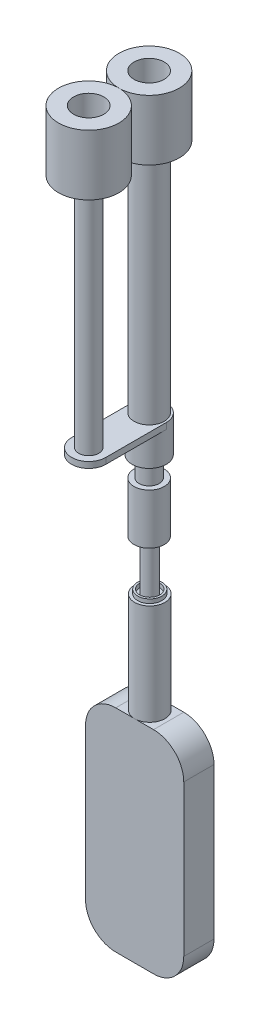
SolidWorks part; units mm, degrees
ref_plane "Front Plane" through (0, 0, 0) normal (0, 0, 1) x (1, 0, 0)
ref_plane "Top Plane" through (0, 0, 0) normal (0, 1, 0) x (1, 0, 0)
ref_plane "Right Plane" through (0, 0, 0) normal (1, 0, 0) x (0, 0, -1)
sketch "Sketch1" plane through (0, 0, 0) normal (0, 0, 1) x (1, 0, 0)
  line L1 (16.25, 35) -> (-16.25, 35)
  line L2 (16.25, 35) -> (16.25, -35)
  line L3 (16.25, -35) -> (-16.25, -35)
  line L4 (-16.25, 35) -> (-16.25, -35)
  line L5 (16.25, 35) -> (-16.25, -35) construction
  line L6 (16.25, -35) -> (-16.25, 35) construction
  point P0 (0, 0)
  dimension "D1" = 32.5
  dimension "D2" = 70
extrude "Boss-Extrude1" add sketch "Sketch1" along normal blind 10
fillet "Fillet1" radius 10 4 edges at (-16.25, -35, 5) (16.25, -35, 5) (16.25, 35, 5) (-16.25, 35, 5)
scale "Scale1" scale about centroid uniform scaling yes scale factor 1.5
sketch "Sketch2" plane through (0, 52.5, 0) normal (0, 1, 0) x (1, 0, 0)
  circle A0 centre (0, -5) radius 7.5
extrude "Boss-Extrude2" add sketch "Sketch2" along normal blind 50
sketch "Sketch3" plane through (0, 102.5, 0) normal (0, 1, 0) x (1, 0, 0)
  circle A0 centre (0, -5) radius 3.5
  dimension "D1" = 7
extrude "Boss-Extrude3" add sketch "Sketch3" along normal blind 25
sketch "Sketch4" plane through (0, 127.5, 0) normal (0, 1, 0) x (1, 0, 0)
  circle A0 centre (0, -5.3071) radius 7.5
  dimension "D1" = 15
extrude "Boss-Extrude4" add sketch "Sketch4" along normal blind 25 contours A0
sketch "Sketch5" plane through (0, 152.5, 0) normal (0, 1, 0) x (1, 0, 0)
  circle A0 centre (0, -5.3071) radius 5
extrude "Boss-Extrude5" add sketch "Sketch5" along normal blind 10
sketch "Sketch6" plane through (0, 162.5, 0) normal (0, 1, 0) x (1, 0, 0)
  circle A0 centre (0, -5.3071) radius 8.5
  dimension "D1" = 17
extrude "Boss-Extrude6" add sketch "Sketch6" along normal blind 15
sketch "Sketch7" plane through (0, 177.5, 0) normal (0, 1, 0) x (1, 0, 0)
  circle A0 centre (0, -5.3071) radius 7.5
  dimension "D1" = 15
extrude "Boss-Extrude7" add sketch "Sketch7" along normal blind 120
ref_plane "Plane3" through (0, 102.5, 0) normal (0, 1, 0) x (1, 0, 0)
sketch "Sketch9" plane through (0, 102.5, 0) normal (0, 1, 0) x (1, 0, 0)
  circle A0 centre (0, -5) radius 6
  circle A1 centre (0, -5) radius 5
  dimension "D1" = 12
  dimension "D2" = 10
extrude "Boss-Extrude8" add sketch "Sketch9" along normal blind 2
ref_plane "Plane4" through (0, 177.5, 0) normal (0, 1, 0) x (1, 0, 0)
sketch "Sketch10" plane through (0, 177.5, 0) normal (0, 1, 0) x (1, 0, 0)
  line L0 (-8.5, -5.3071) -> (-8.5, -35.3071)
  line L1 (8.5, -5.3071) -> (8.5, -35.3071)
  arc A0 (8.5, -5.3071) -> (-8.5, -5.3071) centre (0, -5.3071) ccw
  arc A1 (-8.5, -35.3071) -> (8.5, -35.3071) centre (0, -35.3071) ccw
  dimension "D1" = 30
  dimension "D2" = 30
extrude "Boss-Extrude9" add sketch "Sketch10" along normal blind 3
ref_plane "Plane5" through (0, 297.5, 0) normal (0, 1, 0) x (1, 0, 0)
sketch "Sketch11" plane through (0, 180.5, 0) normal (0, 1, 0) x (1, 0, 0)
  circle A0 centre (0, -35.3071) radius 5
  arc A1 (-8.5, -35.3071) -> (8.5, -35.3071) centre (0, -35.3071) ccw construction
  dimension "D2" = 10
  dimension "D1" = 0
extrude "Boss-Extrude10" add sketch "Sketch11" along normal up to surface (117 mm away) up to plane "Plane5"
sketch "Sketch12" plane through (0, 297.5, 0) normal (0, 1, 0) x (1, 0, 0)
  circle A0 centre (0, -5.3071) radius 15
  circle A1 centre (0, -35.3071) radius 15
  circle M3 centre (0, -5.3071) radius 7.5
  dimension "D1" = 30
  dimension "D2" = 30
extrude "Boss-Extrude11" add sketch "Sketch12" along normal blind 30 contours A1 | A0 M3 region at (10.3066, 297.5, 15.6137) region at (0, 297.5, 35.3071)
sketch "Sketch13" plane through (0, 327.5, 0) normal (0, 1, 0) x (1, 0, 0)
  circle A0 centre (0, -35.3071) radius 7.5
extrude "Cut-Extrude2" cut sketch "Sketch13" against normal blind 30
